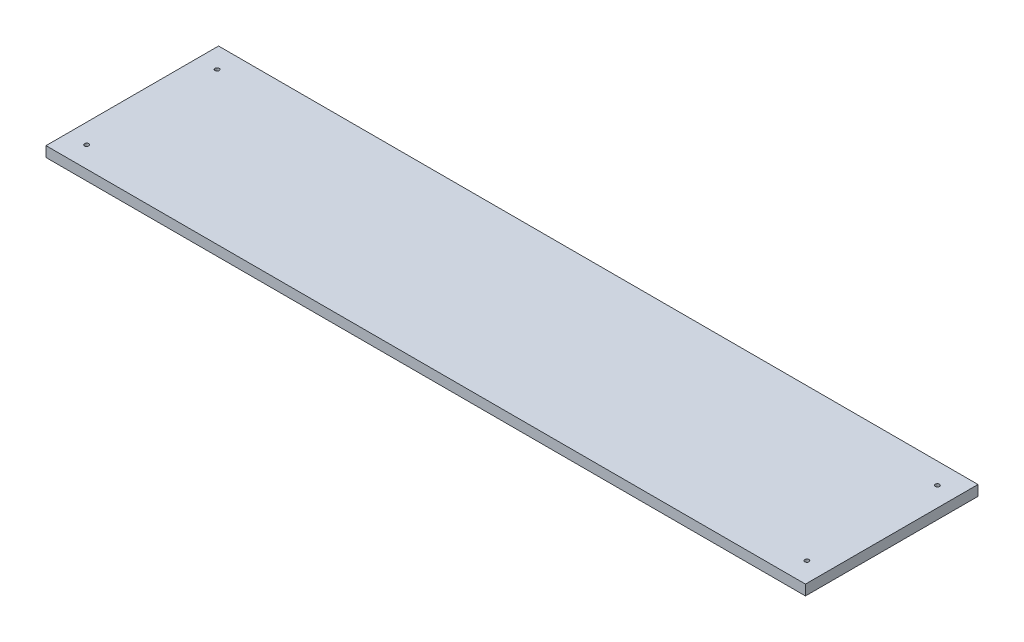
SolidWorks part; units mm, degrees
ref_plane "Front Plane" through (0, 0, 0) normal (0, 0, 1) x (1, 0, 0)
ref_plane "Top Plane" through (0, 0, 0) normal (0, 1, 0) x (1, 0, 0)
ref_plane "Right Plane" through (0, 0, 0) normal (1, 0, 0) x (0, 0, -1)
sketch "Szkic1" plane through (0, 0, 0) normal (0, 1, 0) x (1, 0, 0)
  line L1 (-332.7263, 193.4615) -> (404.0737, 193.4615)
  line L2 (-332.7263, 193.4615) -> (-332.7263, 26.0615)
  line L3 (-332.7263, 26.0615) -> (404.0737, 26.0615)
  line L4 (404.0737, 193.4615) -> (404.0737, 26.0615)
  dimension "D1" = 736.8
  dimension "D2" = 167.4
extrude "Dodanie-wyciągnięcie1" add sketch "Szkic1" along normal blind 10
sketch "Szkic2" plane through (0, 0, 0) normal (0, -1, 0) x (1, 0, 0)
  line L0 (-332.7263, -193.4615) -> (-332.7263, -26.0615) construction
  line L1 (-327.7263, -31.0615) -> (399.0737, -31.0615)
  line L2 (-327.7263, -31.0615) -> (-327.7263, -188.4615)
  line L3 (-327.7263, -188.4615) -> (399.0737, -188.4615)
  line L4 (399.0737, -31.0615) -> (399.0737, -188.4615)
  line L5 (-332.7263, -26.0615) -> (404.0737, -26.0615) construction
  line L6 (404.0737, -193.4615) -> (-332.7263, -193.4615) construction
  line L7 (404.0737, -26.0615) -> (404.0737, -193.4615) construction
  dimension "D1" = 5
  dimension "D2" = 5
  dimension "D3" = 5
  dimension "D4" = 5
extrude "Wycięcie-wyciągnięcie-cienka ścianka1" cut sketch "Szkic2" against normal blind 3 thin thin type mid plane wall 3
sketch "Szkic3" plane through (0, 0, 0) normal (0, -1, 0) x (1, 0, 0)
  line L0 (397.5737, -32.5615) -> (-326.2263, -32.5615) construction
  line L1 (-321.2263, -37.5615) -> (392.5737, -37.5615)
  line L2 (-321.2263, -37.5615) -> (-321.2263, -181.9615)
  line L3 (-321.2263, -181.9615) -> (392.5737, -181.9615)
  line L4 (392.5737, -37.5615) -> (392.5737, -181.9615)
  line L5 (397.5737, -186.9615) -> (397.5737, -32.5615) construction
  line L6 (-326.2263, -186.9615) -> (397.5737, -186.9615) construction
  line L7 (-326.2263, -32.5615) -> (-326.2263, -186.9615) construction
  dimension "D1" = 5
  dimension "D2" = 5
  dimension "D3" = 5
  dimension "D4" = 5
extrude "Wytnij-wyciągnięcie1" cut sketch "Szkic3" against normal blind 5
fillet "Zaokrąglenie1" radius 3 8 edges at (-321.2263, 2.5, -181.9615) (-329.2263, 1.5, -189.9615) (-329.2263, 1.5, -29.5615) (-326.2263, 1.5, -32.5615) (397.5737, 1.5, -32.5615) (400.5737, 1.5, -29.5615) (400.5737, 1.5, -189.9615) (397.5737, 1.5, -186.9615)
sketch "Szkic4" plane through (0, 0, 0) normal (0, -1, 0) x (1, 0, 0)
  line L0 (-332.7263, -193.4615) -> (-332.7263, -26.0615) construction
  line L1 (-332.7263, -26.0615) -> (404.0737, -26.0615) construction
  line L2 (-332.7263, -109.7615) -> (-308.6128, -109.7615)
  line L3 (35.6737, -26.0615) -> (35.6737, -68.6435)
  circle A0 centre (-313.7263, -46.4615) radius 2
  circle A1 centre (-313.7263, -46.4615) radius 4
  circle A2 centre (-313.7263, -173.0615) radius 4
  circle A3 centre (-313.7263, -173.0615) radius 2
  circle A4 centre (-313.7263, -46.4615) radius 2
  circle A5 centre (-313.7263, -46.4615) radius 4
  circle A6 centre (-313.7263, -173.0615) radius 4
  circle A7 centre (-313.7263, -173.0615) radius 2
  circle A8 centre (385.0737, -173.0615) radius 2
  circle A9 centre (385.0737, -173.0615) radius 4
  circle A10 centre (385.0737, -173.0615) radius 2
  circle A11 centre (385.0737, -173.0615) radius 4
  circle A12 centre (385.0737, -46.4615) radius 4
  circle A13 centre (385.0737, -46.4615) radius 2
  circle A14 centre (385.0737, -46.4615) radius 4
  circle A15 centre (385.0737, -46.4615) radius 2
  dimension "D1" = 4
  dimension "D3" = 20.4
  dimension "D4" = 8
  dimension "D2" = 19
extrude "Dodanie-wyciągnięcie2" add sketch "Szkic4" against normal blind 10 contours A2 A3 | A9 A8 | A1 | A12 region at (-317.6131, 0, -173.0615) region at (381.1869, 0, -173.0615)
extrude "Wytnij-wyciągnięcie2" cut sketch "Szkic4<3>" against normal blind 10 contours A8 | A13 | A0 | A3
sketch "Szkic4<3>" plane through (0, 0, 0) normal (0, -1, 0) x (1, 0, 0) same geometry as "Szkic4"
